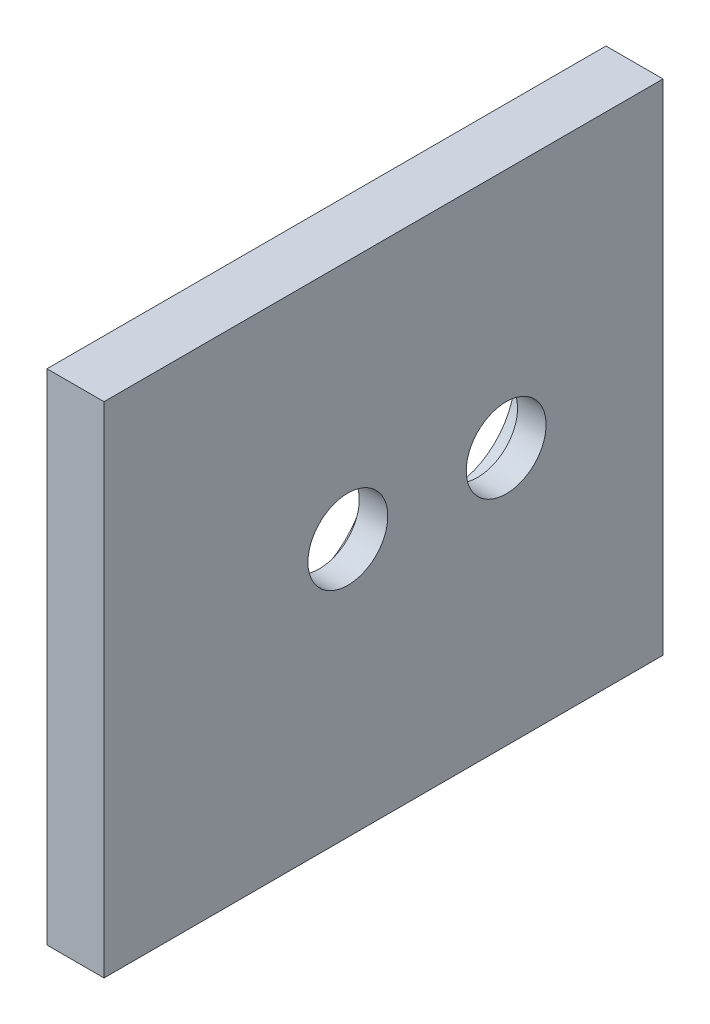
SolidWorks part; units mm, degrees
ref_plane "Front Plane" through (0, 0, 0) normal (0, 0, 1) x (1, 0, 0)
ref_plane "Top Plane" through (0, 0, 0) normal (0, 1, 0) x (1, 0, 0)
ref_plane "Right Plane" through (0, 0, 0) normal (1, 0, 0) x (0, 0, -1)
sketch "Sketch1" plane through (114, 0, 0) normal (0, 1, 0) x (1, 0, 0)
  line L0 (-104, 0) -> (-114, 0) construction
  line L1 (-124, 98) -> (-104, 98)
  line L2 (-124, 98) -> (-124, -98)
  line L3 (-124, -98) -> (-104, -98)
  line L4 (-104, 98) -> (-104, -98)
  line L5 (-114, -96.25) -> (-114, 96.25) construction
  point P9 (-114, -98)
  dimension "D1" = 20
  dimension "D2" = 196
extrude "Boss-Extrude1" add sketch "Sketch1" along normal blind 175
sketch "Sketch2" plane through (-10, 0, 0) normal (-1, 0, 0) x (0, 0, 1)
  line L2 (0, -11) -> (0, 11) construction
  line L3 (0, -96.25) -> (0, 96.25) construction
  line L4 (98, 175) -> (98, 0) construction
  line L5 (-98, 0) -> (98, 0) construction
  line L6 (-98, 175) -> (-98, 0) construction
  circle A1 centre (12.5, 90.5) radius 27.5
  circle A2 centre (-43, 90.5) radius 23
  dimension "D1" = 55
  dimension "D2" = 46
  dimension "D5" = 58
  dimension "D6" = 63
  dimension "D7" = 90.5
  dimension "D8" = 32
  dimension "D3" = 12.5
  dimension "D4" = 43
extrude "Cut-Extrude1" cut sketch "Sketch2" against normal blind 10
sketch "Sketch3" plane through (0, 0, 0) normal (-1, 0, 0) x (0, 0, 1)
  circle A0 centre (12.5, 90.5) radius 14
  circle A1 centre (-43, 90.5) radius 14
  circle A2 centre (-43, 90.5) radius 23 construction
  circle A3 centre (12.5, 90.5) radius 27.5 construction
  dimension "D1" = 28
extrude "Cut-Extrude2" cut sketch "Sketch3" against normal through all
